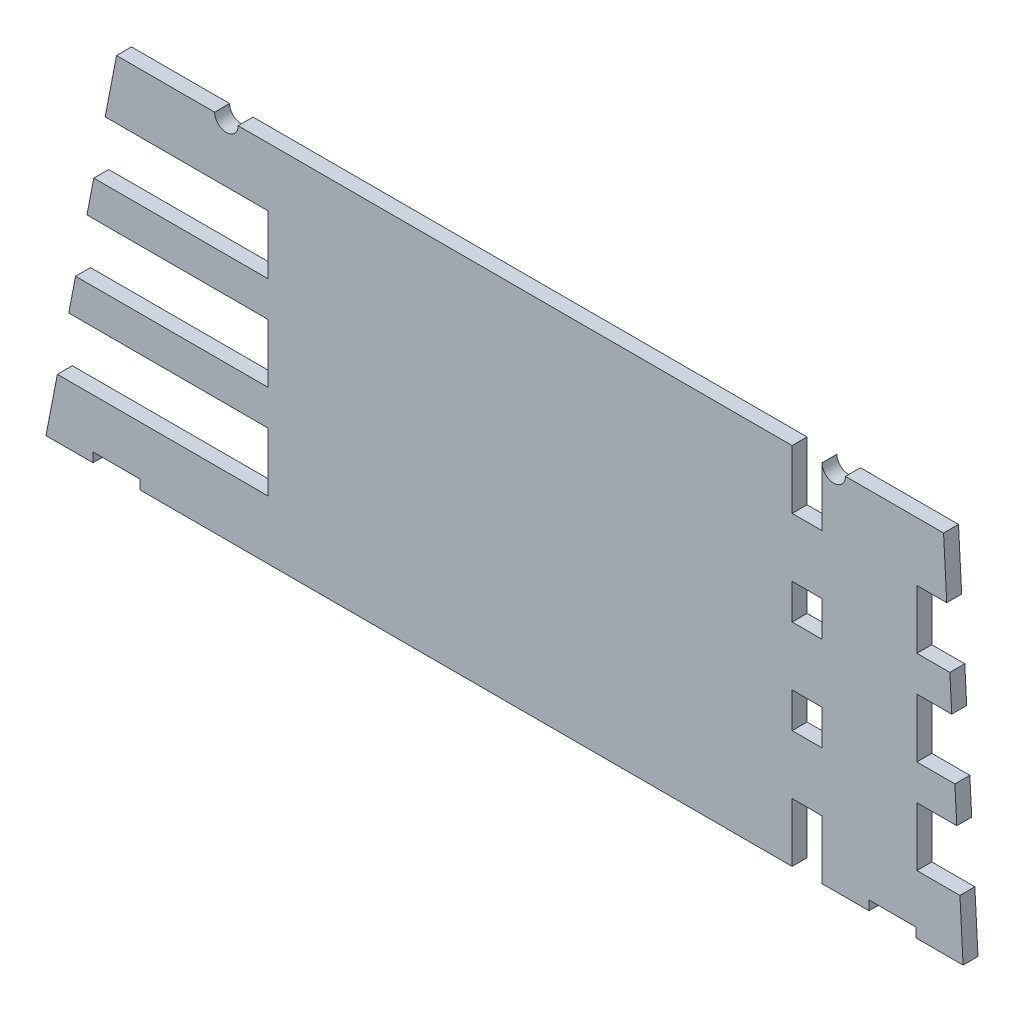
SolidWorks part; units mm, degrees
ref_plane "Front Plane" through (0, 0, 0) normal (0, 0, 1) x (1, 0, 0)
ref_plane "Top Plane" through (0, 0, 0) normal (0, 1, 0) x (1, 0, 0)
ref_plane "Right Plane" through (0, 0, 0) normal (1, 0, 0) x (0, 0, -1)
sketch "Sketch1" plane through (0, 0, 0) normal (0, 0, 1) x (1, 0, 0)
  line L0 (-159.5062, 0) -> (117.7937, 0)
  line L1 (190.4938, 0) -> (189.1571, 25)
  line L2 (182.2063, 155) -> (140.4938, 155)
  line L3 (-169.5063, 155) -> (-174.345, 130)
  line L4 (-199.5062, 0) -> (-179.5062, 0)
  line L5 (-179.5062, 0) -> (-179.5062, 4)
  line L6 (-179.5062, 4) -> (-159.5062, 4)
  line L7 (-159.5062, 4) -> (-159.5062, 0)
  line L8 (-169.5063, 155) -> (-127.7938, 155)
  line L9 (150.4938, 0) -> (150.4938, 4)
  line L10 (150.4938, 4) -> (170.4938, 4)
  line L11 (170.4938, 4) -> (170.4938, 0)
  line L12 (170.4938, 0) -> (190.4938, 0)
  line L13 (-169.5063, 155) -> (-127.7938, 155)
  line L14 (0, 155) -> (0, 0) construction
  line L15 (-117.7938, 155) -> (117.7937, 155)
  line L16 (-174.345, 130) -> (-105.0938, 130)
  line L17 (-105.0938, 130) -> (-105.0938, 105)
  line L18 (-105.0938, 105) -> (-179.1837, 105)
  line L19 (-182.0869, 90) -> (-105.0938, 90)
  line L20 (-105.0938, 90) -> (-105.0937, 65)
  line L21 (-105.0937, 65) -> (-186.9256, 65)
  line L22 (-189.8288, 50) -> (-105.0938, 50)
  line L23 (-105.0938, 50) -> (-105.0938, 25)
  line L24 (-105.0938, 25) -> (-194.6675, 25)
  line L25 (-179.1837, 105) -> (-182.0869, 90)
  line L26 (-186.9256, 65) -> (-189.8288, 50)
  line L27 (-194.6675, 25) -> (-199.5062, 0)
  line L28 (117.7937, 90) -> (117.7937, 105)
  line L29 (117.7937, 105) -> (130.4937, 105)
  line L30 (130.4937, 105) -> (130.4938, 90)
  line L31 (130.4938, 90) -> (117.7937, 90)
  line L32 (-105.0938, 105) -> (-105.0938, 90) construction
  line L33 (117.7937, 50) -> (117.7937, 65)
  line L34 (117.7937, 65) -> (130.4938, 65)
  line L35 (130.4938, 65) -> (130.4938, 50)
  line L36 (130.4938, 50) -> (117.7937, 50)
  line L37 (130.4938, 0) -> (130.4938, 25)
  line L38 (130.4938, 25) -> (117.7937, 25)
  line L39 (117.7937, 25) -> (117.7937, 0)
  line L40 (117.7937, 155) -> (117.7937, 130)
  line L41 (117.7937, 130) -> (130.4938, 130)
  line L42 (130.4938, 130) -> (130.4938, 155)
  line L43 (130.4938, 0) -> (150.4938, 0)
  line L44 (183.5429, 130) -> (170.8429, 130)
  line L45 (170.8429, 130) -> (170.8429, 105)
  line L46 (170.8429, 105) -> (184.8796, 105)
  line L47 (185.6817, 90) -> (170.8429, 90)
  line L48 (170.8429, 90) -> (170.8429, 65)
  line L49 (170.8429, 65) -> (187.0183, 65)
  line L50 (187.8204, 50) -> (170.8429, 50)
  line L51 (170.8429, 50) -> (170.8429, 25)
  line L52 (170.8429, 25) -> (189.1571, 25)
  line L53 (183.5429, 130) -> (182.2063, 155)
  line L54 (185.6817, 90) -> (184.8796, 105)
  line L55 (187.8204, 50) -> (187.0183, 65)
  arc A0 (-127.7938, 155) -> (-117.7938, 155) centre (-122.7938, 155) ccw
  arc A1 (140.4938, 155) -> (130.4938, 155) centre (135.4938, 155) cw
  dimension "D2" = 20
  dimension "D3" = 20
  dimension "D4" = 268.2875
  dimension "D5" = 15
  dimension "D6" = 10
  dimension "D7" = 12.7
  dimension "D8" = 4
  dimension "D9" = 10
  dimension "D10" = 310
  dimension "D11" = 5
  dimension "D12" = 25
  dimension "D13" = 12.7
  dimension "D14" = 25
  dimension "D15" = 12.7
  dimension "D16" = 155
extrude "Extrude1" add sketch "Sketch1" along normal blind 6.35 contours L0 L15 A0 L8 L3 L4 L5 L6 L7 | L0 L9 L10 L11 L12 L1 L2 A1 L15 region at (11.7671, 76.4866, 0)
